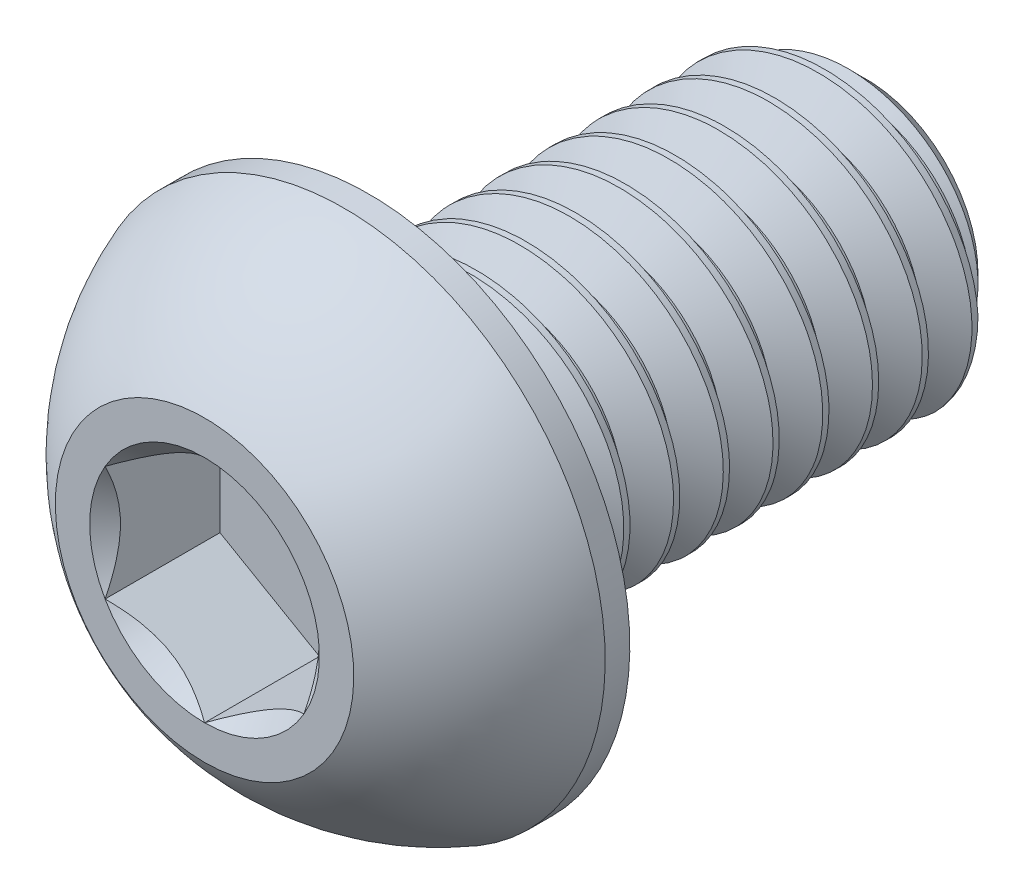
SolidWorks part; units mm, degrees
ref_plane "Front" through (0, 0, 0) normal (0, 0, 1) x (1, 0, 0)
ref_plane "Top" through (0, 0, 0) normal (0, 1, 0) x (1, 0, 0)
ref_plane "Right" through (0, 0, 0) normal (1, 0, 0) x (0, 0, -1)
sketch "Sketch1" plane through (0, 0, 0) normal (1, 0, 0) x (0, 0, -1)
  line L2 (-5, 3) -> (5, 3)
  line L3 (5, 3) -> (5, 0)
  line L4 (5, 0) -> (-5, 0)
  line L6 (-5.495, 5.25) -> (-5, 5.25) construction
  line L7 (5, 3) -> (5, -3) construction
  line L8 (-8.3, 0) -> (-5, 0) construction
  line L9 (-5, 5.25) -> (-5, -5.25) construction
  line L11 (-5, 3) -> (-5, 0)
  line L13 (-8.3, 2) -> (-8.3, -2) construction
  line L14 (-8.3, 2) -> (-8.3, 3) construction
  line L15 (4.9375, 3.1083) -> (5.4375, 2.2422) construction
  line L16 (5.4375, 2.2422) -> (5.9375, 3.1083) construction
  line L17 (5.9375, 3.1083) -> (4.9375, 3.1083) construction
  line L18 (5, 3) -> (5.875, 3) construction
  line L19 (5.4375, 3.1083) -> (5.4375, 3) construction
  line L20 (5.4375, 3) -> (5.4375, 2.3505) construction
  line L21 (5.4375, 2.3505) -> (5.4375, 2.2422) construction
  line L22 (5.375, 2.3505) -> (5.5, 2.3505)
  line L23 (4.9688, 3.0541) -> (5.9063, 3.0541)
  line L24 (5.5, 2.3505) -> (5.9063, 3.0541)
  line L25 (5.375, 2.3505) -> (4.9688, 3.0541)
  line L26 (4.25, 3) -> (5, 2.25)
  arc A3 (-8.3, 3) -> (-5.495, 5.25) centre (-3.5887, 0) cw construction
  point P29 (5.4375, 3.0541)
  point P30 (2.5, -3)
  point P33 (0, 0)
  dimension "Thread Size" = 6
  dimension "D1" = 0.495
  dimension "Head Height" = 3.3
  dimension "Head Diameter" = 10.5
  dimension "Length" = 10
  dimension "Drive Size" = 4
  dimension "Thread Pitch" = 1
  dimension "D3" = 0.125
  dimension "D2" = 0.75
  dimension "D4" = 45
  dimension "D5" = 2.5
sketch "Sketch10" plane through (0, 0, 0) normal (1, 0, 0) x (0, 0, -1)
  line L0 (4.25, 3) -> (5, 2.25) construction
  line L1 (4.25, 3) -> (5, 2.25)
  line L4 (5, 3) -> (-5, 3)
  line L5 (5, 0) -> (5, 3)
  line L6 (-5, 0) -> (5, 0)
  line L7 (-5, 3) -> (-5, 0)
  line L8 (4.25, 3) -> (-5, 3)
  line L9 (5, 0) -> (5, 2.25)
  line L10 (-5, 0) -> (5, 0)
  line L11 (-5, 3) -> (-5, 0)
  dimension "D1" = 0
revolve "Revolve3" add sketch "Sketch10" angle 360 about L8
sketch "Sketch7" plane through (0, 0, 0) normal (1, 0, 0) x (0, 0, -1)
  line L6 (-5.495, 5.25) -> (-5, 5.25) construction
  line L8 (-8.3, 0) -> (-5, 0) construction
  line L11 (-5, 5.25) -> (-5, -5.25) construction
  line L12 (-5.495, 5.25) -> (-5, 5.25)
  line L13 (-8.3, 0) -> (-5, 0)
  line L14 (-8.3, 2) -> (-8.3, -2) construction
  line L15 (-5, 5.25) -> (-5, 0)
  line L16 (-8.3, 3) -> (-8.3, 0)
  arc A2 (-5.495, 5.25) -> (-8.3, 3) centre (-3.5887, 0) ccw construction
  arc A3 (-5.495, 5.25) -> (-8.3, 3) centre (-3.5887, 0) ccw
revolve "Revolve2" add sketch "Sketch7" angle 360 mid plane about L13
sketch "Sketch5" plane through (0, 0, 8.3) normal (0, 0, 1) x (1, 0, 0)
  line L1 (2, -1.1547) -> (2, 1.1547)
  line L2 (2, 1.1547) -> (0, 2.3094)
  line L3 (0, 2.3094) -> (-2, 1.1547)
  line L4 (-2, 1.1547) -> (-2, -1.1547)
  line L5 (-2, -1.1547) -> (0, -2.3094)
  line L6 (0, -2.3094) -> (2, -1.1547)
  circle A0 centre (0, 0) radius 2 construction
extrude "Cut-Extrude2" cut sketch "Sketch5" against normal blind 2.31
sketch "Sketch6" plane through (0, 0, 8.3) normal (0, 0, 1) x (1, 0, 0)
  circle A0 centre (0, 0) radius 2.3094
extrude "Cut-Extrude3" cut sketch "Sketch6" against normal blind 2.31 draft 45
sketch "Sketch9" plane through (0, 0, 5) normal (0, 0, -1) x (-1, 0, 0)
  circle A0 centre (0, 0) radius 3 construction
  circle A4 centre (0, 0) radius 3
split "Split1" bodies to split 113 resulting bodies 123 124 split by face at (0, -5.25, 5)
sketch "Sketch11" plane through (0, 0, -5) normal (0, 0, -1) x (-1, 0, 0)
  circle A0 centre (0, 0) radius 3 construction
  circle A1 centre (0, 0) radius 3
curve "Helix/Spiral1" pitch 1 height 13.3 radius 3 centre (0, 0, -5) axis (0, 0, 1) start towards (0, 1, 0)
sketch "Sketch12" plane through (0, 0, 0) normal (1, 0, 0) x (0, 0, -1)
  line L0 (5.375, 2.3505) -> (5.5, 2.3505) construction
  line L1 (5.5, 2.3505) -> (5.9063, 3.0541) construction
  line L2 (4.9688, 3.0541) -> (5.9063, 3.0541) construction
  line L3 (5.375, 2.3505) -> (4.9688, 3.0541) construction
  line L4 (5.375, 2.3505) -> (5.5, 2.3505)
  line L5 (5.5, 2.3505) -> (5.9063, 3.0541)
  line L6 (4.9688, 3.0541) -> (5.9063, 3.0541)
  line L7 (5.375, 2.3505) -> (4.9688, 3.0541)
sweep "Cut-Sweep2" cut profiles "Sketch12" path "Helix/Spiral1" align with end faces yes
extrude "Boss-Extrude1" add sketch "Sketch9" along normal blind 10 draft 45
sketch "Sketch13" plane through (0, 0, 0) normal (0, 1, 0) x (1, 0, 0)
  line L0 (0, -8.3) -> (0, 5) construction
  line L1 (2.25, 5) -> (-2.25, 5) construction
ref_axis "Axis1" through (0, 0, 8.3) along (0, 0, -1)
equation "\"D1@Cut-Extrude2\" = \"Head Height@Sketch1\" * .7"
equation "\"D1@Sketch1\" = \"Head Height@Sketch1\" * .15"
equation "\"D1@Cut-Extrude3\" = \"D1@Cut-Extrude2\""
equation "\"D3@Sketch1\" = \"Thread Pitch@Sketch1\" / 8"
equation "\"D2@Sketch1\" = \"Thread Pitch@Sketch1\" * 0.75"
equation "\"D3@Helix/Spiral1\" = \"Length@Sketch1\" + \"Head Height@Sketch1\""
equation "\"D4@Helix/Spiral1\" = \"Thread Pitch@Sketch1\""
equation "\"D5@Sketch1\" = \"Thread Pitch@Sketch1\" * 2.5"
